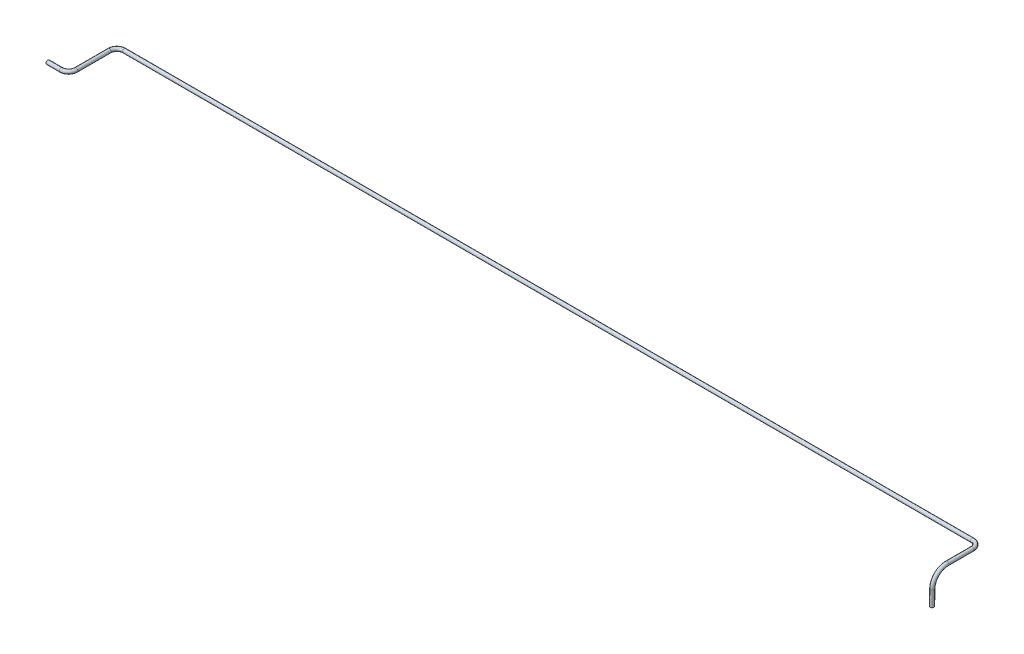
SolidWorks part; units mm, degrees
ref_plane "Front Plane" through (0, 0, 0) normal (0, 0, 1) x (1, 0, 0)
ref_plane "Top Plane" through (0, 0, 0) normal (0, 1, 0) x (1, 0, 0)
ref_plane "Right Plane" through (0, 0, 0) normal (1, 0, 0) x (0, 0, -1)
sketch3d "3DSketch1"
  line L1 (0, 0, 0) -> (22.86, 0, 0)
  line L2 (35.56, 0, -12.7) -> (35.56, 0, -69.85)
  line L3 (48.26, 0, -82.55) -> (1499.6587, 0, -82.55)
  line L4 (1512.3587, 0, -69.85) -> (1512.3587, 0, -26.7385)
  line L5 (1512.3587, -24.9567, -1.3424) -> (1512.3587, -50.7923, -0.8914)
  arc A0 (1512.3587, 0, -69.85) -> (1499.6587, 0, -82.55) centre (1499.6587, 0, -69.85) ccw
  arc A1 (35.56, 0, -69.85) -> (48.26, 0, -82.55) centre (48.26, 0, -69.85) ccw
  arc A2 (22.86, 0, 0) -> (35.56, 0, -12.7) centre (22.86, 0, -12.7) ccw
  arc A3 (1512.3587, 0, -26.7385) -> (1512.3587, -24.9567, -1.3424) centre (1512.3587, -25.4, -26.7385) ccw
  point P9 (1512.3587, 0, -82.55)
  point P10 (1499.6587, 12.7, -69.85)
  point P12 (1512.3587, 0, -1.778)
  point P16 (35.56, 0, -82.55)
  point P17 (48.26, -12.7, -69.85)
  point P20 (35.56, 0, 0)
  point P22 (22.86, 12.7, -12.7)
  point P23 (1537.7587, -25.4, -26.7385)
  dimension "D9" = 1513.2117
  dimension "D10" = 25.4
  dimension "D6" = 12.7
  dimension "D7" = 12.7
  dimension "D8" = 91
  dimension "D1" = 35.56
  dimension "D2" = 82.55
  dimension "D3" = 1476.7987
  dimension "D4" = 80.772
  dimension "D5" = 50.8
ref_plane "Plane4" through (0, 0, 0) normal (1, 0, 0) x (0, 0, -1)
sketch "Sketch5" plane through (0, 0, 0) normal (1, 0, 0) x (0, 0, -1)
  circle A0 centre (0, 0) radius 3.175
  circle A1 centre (0, 0) radius 2.667
  dimension "D1" = 6.35
  dimension "D2" = 0.508
sweep "Sweep3" add profiles "Sketch5" path "3DSketch1"
